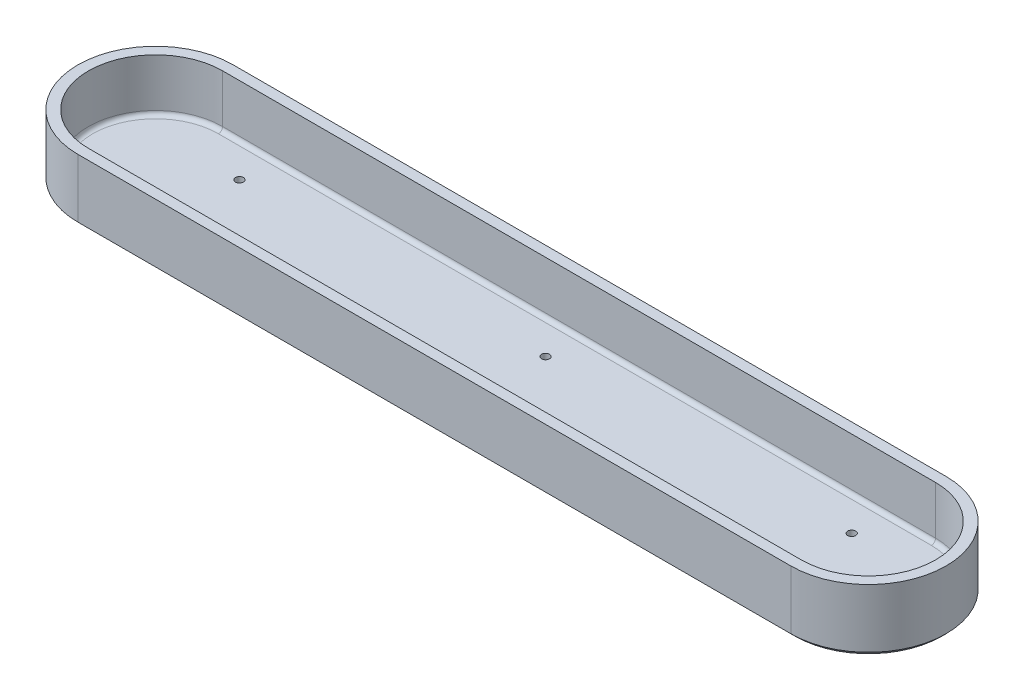
SolidWorks part; units mm, degrees
ref_plane "Front Plane" through (0, 0, 0) normal (0, 0, 1) x (1, 0, 0)
ref_plane "Top Plane" through (0, 0, 0) normal (0, 1, 0) x (1, 0, 0)
ref_plane "Right Plane" through (0, 0, 0) normal (1, 0, 0) x (0, 0, -1)
sketch "Sketch1" plane through (0, 0, 0) normal (0, 1, 0) x (1, 0, 0)
  line L0 (-107.95, 0) -> (107.95, 0) construction
  line L1 (0, -55.9739) -> (0, 55.9739) construction
  line L2 (-107.95, 20.32) -> (107.95, 20.32)
  line L3 (-107.95, -20.32) -> (107.95, -20.32)
  arc A0 (-107.95, 20.32) -> (-107.95, -20.32) centre (-107.95, 0) ccw
  arc A1 (107.95, 20.32) -> (107.95, -20.32) centre (107.95, 0) cw
  point P4 (0, 0)
  point P10 (0, 0)
  dimension "D2" = 40.64
  dimension "D1" = 215.9
extrude "MainBlock" add sketch "Sketch1" along normal blind 3.175
sketch "Sketch2" plane through (0, 0, 0) normal (0, -1, 0) x (1, 0, 0)
  line L0 (0, 0) -> (0, 50000) construction
  line L1 (-107.95, 23.495) -> (107.95, 23.495)
  line L2 (-107.95, -20.32) -> (107.95, -20.32)
  line L3 (107.95, 20.32) -> (-107.95, 20.32)
  line L5 (107.95, 20.32) -> (-107.95, 20.32)
  line L6 (-95.25, 0) -> (49904.75, 0) construction
  line L7 (107.95, -20.32) -> (-107.95, -20.32)
  line L8 (-107.95, -23.495) -> (107.95, -23.495)
  arc A0 (-107.95, 23.495) -> (-107.95, -23.495) centre (-107.95, 0) ccw
  arc A1 (107.95, 20.32) -> (107.95, -20.32) centre (107.95, 0) cw
  arc A2 (-107.95, 20.32) -> (-107.95, -20.32) centre (-107.95, 0) ccw
  arc A3 (107.95, -20.32) -> (107.95, 20.32) centre (107.95, 0) ccw
  arc A4 (-107.95, 20.32) -> (-107.95, -20.32) centre (-107.95, 0) ccw
  arc A6 (107.95, 23.495) -> (107.95, -23.495) centre (107.95, 0) cw
  point P0 (0, 20.32)
  point P15 (0, 23.495)
  point P16 (0, -20.32)
  point P19 (0, -23.495)
  dimension "2.1" = 46.99
  dimension "D1" = 0
extrude "Boss-Extrude1" add sketch "Sketch2" against normal blind 19.05
sketch "Sketch3" plane through (0, 0, 0) normal (0, -1, 0) x (1, 0, 0)
  line L0 (0, 0) -> (50000, 0) construction
  line L1 (0, 0) -> (0, 50000) construction
  line L2 (-107.95, 0.9216) -> (-107.95, 50000.9216) construction
  arc A0 (-107.95, 23.495) -> (-107.95, -23.495) centre (-107.95, 0) ccw construction
  arc A1 (-107.95, 23.495) -> (-107.95, -23.495) centre (-107.95, 0) ccw construction
  circle A2 centre (0, 10.16) radius 1.2065
  circle A3 centre (-92.71, 10.16) radius 1.2065
  circle A4 centre (92.71, 10.16) radius 1.2065
  circle A5 centre (92.71, -10.16) radius 1.2065
  circle A6 centre (-92.71, -10.16) radius 1.2065
  circle A7 centre (0, -10.16) radius 1.2065
  dimension "D1" = 2.413
  dimension "D4" = 2.413
  dimension "D2" = 10.16
  dimension "D3" = 10.16
  dimension "D5" = 15.24
extrude "Cut-Extrude1" cut sketch "Sketch3" against normal through all
fillet "Fillet1" radius 1.27 4 edges at (128.27, 3.175, 0) (0, 3.175, 20.32) (-128.27, 3.175, 0) (0, 3.175, -20.32)
chamfer "Chamfer1" distance 1.27 angle 45 4 edges at (0, 0, 23.495) (-131.445, 0, 0) (131.445, 0, 0) (0, 0, -23.495)
equation "\"D4@Sketch3\"=\"D1@Sketch3\""
